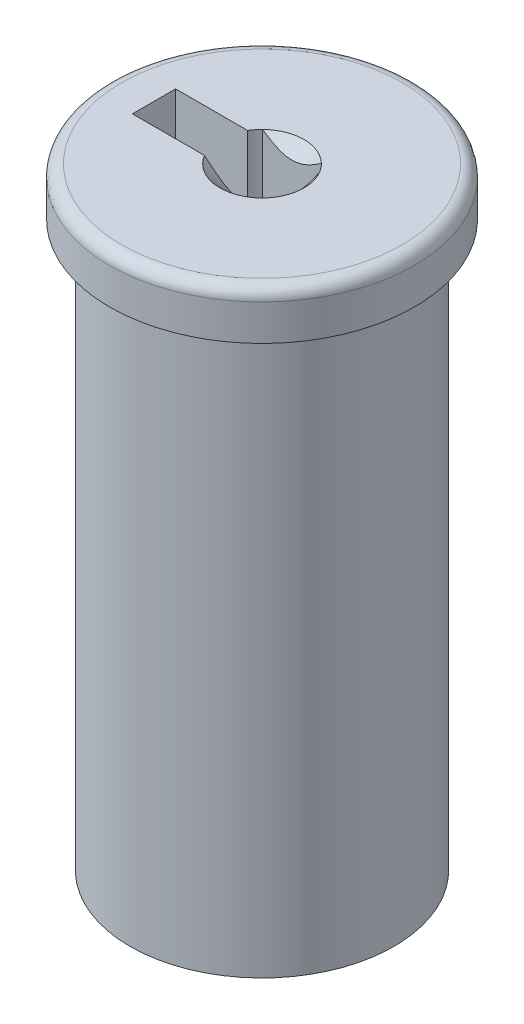
SolidWorks part; units mm, degrees
material "AISI 304"
ref_plane "Front Plane" through (0, 0, 0) normal (0, 0, 1) x (1, 0, 0)
ref_plane "Top Plane" through (0, 0, 0) normal (0, 1, 0) x (1, 0, 0)
ref_plane "Right Plane" through (0, 0, 0) normal (1, 0, 0) x (0, 0, -1)
ref_plane "Plane1" through (0, 0, 0) normal (0, 0, -1) x (-1, 0, 0)
sketch "Sketch1" plane through (0, 0, 0) normal (0, 0, -1) x (-1, 0, 0)
  line L0 (-6.35, 0) -> (0, 0)
  line L1 (0, 0) -> (0, 1.9969)
  line L2 (0, 1.9969) -> (-6.35, 1.9969)
  line L3 (-6.35, 1.9969) -> (-6.35, 0)
  line L4 (0, 0) -> (0, 1.9969) construction
  line L5 (0, 15.1405) -> (0, -4.2223) construction
  point P7 (0, 0)
  dimension "D1" = 12.7
  dimension "D2" = 1.9969
revolve "Revolve1" add sketch "Sketch1" angle 360 about L4 reverse direction yes
sketch "Sketch2" plane through (0, 0, 0) normal (0, -1, 0) x (1, 0, 0)
  circle A0 centre (0, 0) radius 5.5
  point P2 (0, 0)
  dimension "D1" = 11
extrude "Boss-Extrude1" add sketch "Sketch2" along normal blind 23.5
sketch "Sketch3" plane through (0, 1.9969, 0) normal (0, 1, 0) x (-1, 0, 0)
  line L0 (4.4992, 0.9) -> (4.4992, -0.9)
  line L1 (4.4992, -0.9) -> (1.5008, -0.9)
  line L2 (-1.5008, -1.25) -> (-1.5008, 0.9)
  line L3 (-1.5008, 0.9) -> (4.4992, 0.9)
  line L4 (-7.8454, 0) -> (6.6625, 0) construction
  line L5 (1.5008, -0.9) -> (1.5008, -1.25)
  line L6 (1.5008, -1.25) -> (-1.5008, -1.25)
  circle A0 centre (0, 0) radius 1.75
  point P9 (0, 0)
  point P13 (-1.4361, -1.5355)
  dimension "D1" = 3.5
  dimension "D2" = 1.8
  dimension "D3" = 6
  dimension "D4" = 2.15
extrude "Cut-Extrude1" cut sketch "Sketch3" against normal blind 10 contours L2 L4 A0 L3 | A0 L4 L0 L3 | L4 A0 L1 L0 | L4 L2 A0 L6 region at (-3.0834, 1.9969, 0.4565) region at (-3.0834, 1.9969, -0.4565) region at (-0.0852, 1.9969, 0.4442) region at (-0.0637, 1.9969, -0.6018)
fillet "Fillet1" radius 0.5 1 edges at (0, 1.9969, 6.35) tangent propagation no
extrude "Cut-Extrude2" cut sketch "Sketch3<3>" against normal blind 2 draft 45 contours L3 A0 | A0 L4 L2 | L4 A0 L2 | L6 A0 | A0 region at (0, 1.9969, 1.2482) region at (1.6011, 1.9969, 0.341) region at (1.6011, 1.9969, -0.341) region at (0, 1.9969, -1.4527)
sketch "Sketch3<3>" plane through (0, 1.9969, 0) normal (0, 1, 0) x (-1, 0, 0) same geometry as "Sketch3"
